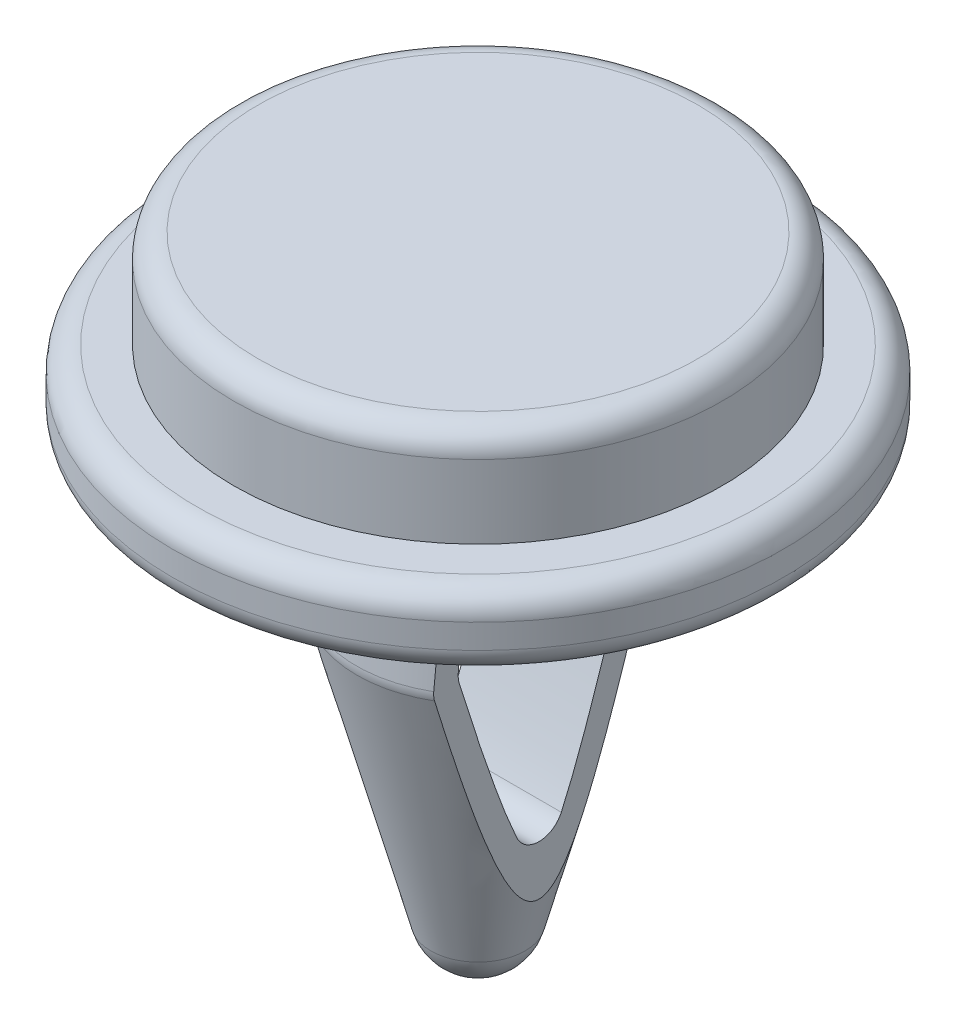
SolidWorks part; units mm, degrees
ref_plane "Front Plane" through (0, 0, 0) normal (0, 0, 1) x (1, 0, 0)
ref_plane "Top Plane" through (0, 0, 0) normal (0, 1, 0) x (1, 0, 0)
ref_plane "Right Plane" through (0, 0, 0) normal (1, 0, 0) x (0, 0, -1)
sketch "Sketch1" plane through (0, 0, 0) normal (0, 0, 1) x (1, 0, 0)
  line L0 (0, 0) -> (0, -15.6223) construction
  line L1 (0, 3.5) -> (5, 3.5)
  line L2 (5, 3.5) -> (5, 1.5)
  line L3 (5, 1.5) -> (6.25, 1.5)
  line L4 (6.25, 1.5) -> (6.25, 0)
  line L5 (6.25, 0) -> (2.2346, 0)
  line L6 (2.2346, 0) -> (2.5, -3.0336)
  line L7 (2.5, -3.0336) -> (0.9659, -8.7588)
  line L8 (0, 3.5) -> (0, -9.5)
  arc A0 (0.9659, -8.7588) -> (0, -9.5) centre (0, -8.5) cw
  dimension "D9" = 1
  dimension "D1" = 10
  dimension "D2" = 2
  dimension "D3" = 12.5
  dimension "D4" = 3.5
  dimension "D5" = 9.5
  dimension "D6" = 5
  dimension "D8" = 15
  dimension "D7" = 85
revolve "Revolve1" add sketch "Sketch1" angle 360 about L0
sketch "Sketch2" plane through (0, 0, 0) normal (0, 0, 1) x (1, 0, 0)
  line L0 (0, 0) -> (0, -10.0413) construction
  line L2 (-4.7977, 0) -> (-1.25, 0)
  line L3 (-4.7977, 0) -> (-4.7977, -10.0413)
  line L4 (-4.7977, -10.0413) -> (-1.25, -10.0413)
  line L5 (-1.25, 0) -> (-1.25, -10.0413)
  line L6 (1.25, 0) -> (1.25, -10.0413)
  line L7 (4.7977, -10.0413) -> (1.25, -10.0413)
  line L8 (4.7977, 0) -> (4.7977, -10.0413)
  line L9 (4.7977, 0) -> (1.25, 0)
  line L10 (-6.25, 0) -> (6.25, 0) construction
  dimension "D1" = 2.5
extrude "Cut-Extrude1" cut sketch "Sketch2" against normal mid plane 11.4745
sketch "Sketch3" plane through (1.25, 0, 0) normal (1, 0, 0) x (0, 0, -1)
  line L3 (1.4021, -0.5) -> (-1.4021, -0.5)
  line L4 (1.0394, -0.5) -> (-1.0394, -0.5)
  arc A0 (0.4549, -6.3871) -> (-0.4549, -6.3871) centre (0, -6.1796) cw
  arc A1 (1.6334, -3.0601) -> (1.655, -2.8819) centre (1.1559, -2.9117) ccw
  arc A2 (-1.6334, -3.0601) -> (-1.655, -2.8819) centre (-1.1559, -2.9117) cw
  arc A3 (-1.0394, -0.5) -> (-1.5384, -0.9689) centre (-1.0394, -1) ccw
  arc A4 (1.0394, -0.5) -> (1.5384, -0.9689) centre (1.0394, -1) cw
  spline S9 degree 3 poles (1900.5006, -627.1403) (-28.7411, 92.9218) (13.0983, 28.6687) (0.8023, -5.5442) (0.6635, -5.9156) (0.4311, -6.4431) (0.3485, -6.6185) (0.2201, -6.8536) (0.1762, -6.9272) (0.1077, -7.0289) (0.0839, -7.0621) (-3.4183, -11.5705) (28.0083, 95.3244) (1666.7454, 1096.5496) knots -22.079978 -22.079978 -22.079978 -22.079978 0.5 0.5 0.75 0.75 0.875 0.875 0.9375 0.9375 0.96875 0.96875 5.889395 5.889395 5.889395 5.889395 only from (1.6874, -2.8858) to (0.0001, -7.1623)
  spline S10 degree 3 poles (1982.9692, 128.7015) (58.1522, 238.7946) (11.1245, 120.5428) (-1.4811, -1.2589) (-1.5073, -1.5119) (-1.5333, -1.7648) (-1.5592, -2.0178) (-14.4581, -128.0164) (5.3687, -257.3728) (-1982.6657, -160.6376) knots -0.366594 -0.366594 -0.366594 -0.366594 0.000763 0.000763 0.000763 0.001526 0.001526 0.001526 0.381497 0.381497 0.381497 0.381497 only from (-1.4021, -0.5) to (-1.6574, -2.9827)
  spline S11 degree 3 poles (-1928.8259, -534.0902) (31.2746, 81.2396) (-13.0583, 28.7174) (-0.8256, -5.481) (-0.695, -5.8337) (-0.4727, -6.3517) (-0.3947, -6.5228) (-0.2648, -6.774) (-0.2189, -6.8566) (2.3251, -10.8924) (9.0226, -12.0178) (1666.2337, 1098.3776) knots -23.381841 -23.381841 -23.381841 -23.381841 0.5 0.5 0.75 0.75 0.875 0.875 0.9375 0.9375 4.046519 4.046519 4.046519 4.046519 only from (-1.6574, -2.9827) to (0.0001, -7.1623)
  spline S12 degree 3 poles (1982.6244, -161.7191) (-4.2859, -257.3197) (14.437, -128.1566) (1.5803, -2.2237) (1.5544, -1.9706) (1.5285, -1.7176) (1.5024, -1.4647) (-11.072, 120.4074) (-57.0662, 238.8473) (-1982.9494, 129.9183) knots -0.379 -0.379 -0.379 -0.379 0.000763 0.000763 0.000763 0.001526 0.001526 0.001526 0.369083 0.369083 0.369083 0.369083 only from (1.6574, -2.9827) to (1.4021, -0.5)
  spline S13 degree 3 poles (-1.5384, -0.9689) (-1.5443, -1.063) (-1.5502, -1.157) (-1.556, -1.2511) (-1.5717, -1.5052) (-1.5873, -1.7593) (-1.6027, -2.0134) (-1.6203, -2.3029) (-1.6377, -2.5924) (-1.655, -2.8819) knots 0.00048 0.00048 0.00048 0.00048 0.000763 0.000763 0.000763 0.001526 0.001526 0.001526 0.002395 0.002395 0.002395 0.002395
  spline S14 degree 3 poles (-1.6334, -3.0601) (-1.418, -3.7528) (-1.1967, -4.4436) (-0.8256, -5.481) (-0.695, -5.8337) (-0.5169, -6.2487) (-0.4864, -6.3181) (-0.4549, -6.3871) knots 0.017941 0.017941 0.017941 0.017941 0.5 0.5 0.75 0.75 0.800431 0.800431 0.800431 0.800431
  spline S15 degree 3 poles (1.655, -2.8819) (1.6418, -2.6613) (1.6286, -2.4407) (1.6152, -2.2201) (1.5999, -1.966) (1.5844, -1.7119) (1.5687, -1.4578) (1.5587, -1.2948) (1.5486, -1.1319) (1.5384, -0.9689) knots 0.000101 0.000101 0.000101 0.000101 0.000763 0.000763 0.000763 0.001526 0.001526 0.001526 0.002015 0.002015 0.002015 0.002015
  spline S16 degree 3 poles (1.6334, -3.0601) (1.4123, -3.7713) (1.1859, -4.4768) (0.8023, -5.5442) (0.6635, -5.9156) (0.491, -6.3073) (0.473, -6.3473) (0.4549, -6.3871) knots 0.037735 0.037735 0.037735 0.037735 0.5 0.5 0.75 0.75 0.77848 0.77848 0.77848 0.77848
  dimension "D3" = 0.5
  dimension "D1" = 0.5
  dimension "D2" = 0.5
extrude "Cut-Extrude2" cut sketch "Sketch3" against normal through all
fillet "Fillet1" radius 0.5 9 edges at (0, 0, 2.2346) (-1.25, 0, 0) (0, 0, -2.2346) (1.25, 0, 0) (0, -3.0336, -2.5) (0, -3.0336, 2.5) (0, 0, 6.25) (0, 1.5, 6.25) (0, 3.5, 5)
